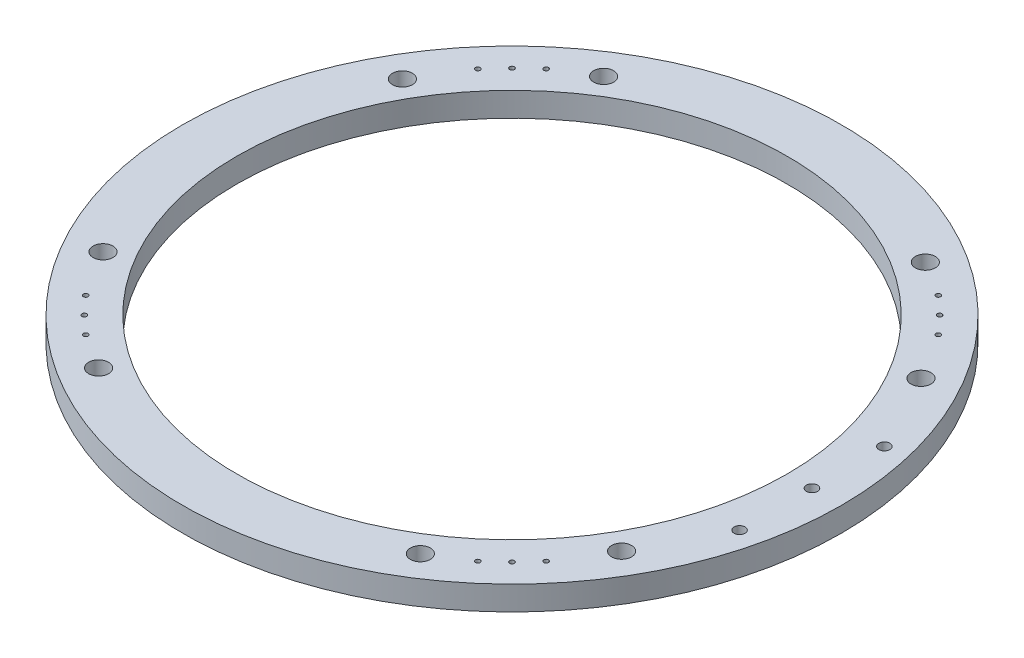
SolidWorks part; units mm, degrees
material "Oak"
ref_plane "Front Plane" through (0, 0, 0) normal (0, 0, 1) x (1, 0, 0)
ref_plane "Top Plane" through (0, 0, 0) normal (0, 1, 0) x (1, 0, 0)
ref_plane "Right Plane" through (0, 0, 0) normal (1, 0, 0) x (0, 0, -1)
sketch "Sketch1" plane through (0, 0, 0) normal (0, 0, 1) x (1, 0, 0)
  line L0 (0, 1125.8152) -> (0, -48874.1848) construction
  line L1 (144.7872, 1009.8532) -> (152.4, 1009.8532)
  line L9 (144.7872, 1022.5532) -> (173.3622, 1022.5532)
  line L10 (144.7872, 1022.5532) -> (144.7872, 1009.8532)
  line L11 (144.7872, 1009.8532) -> (173.3622, 1009.8532)
  line L12 (173.3622, 1022.5532) -> (173.3622, 1009.8532)
revolve "Revolve1" add sketch "Sketch1" angle 360 about L0 region at (159.0747, 1016.2032, 0)
hole_wizard "Tap Drill for M3x0.5 Tap1" positions "Sketch9" profile "Sketch10" hole size "M3x0.5" standard "ANSI Metric" end condition through all
sketch "Sketch9" plane through (0, 1009.8532, 0) normal (0, -1, 0) x (-1, 0, 0)
  line L0 (0, 0) -> (112.4828, 112.4828) construction
  line L3 (0, 0) -> (103.1435, 121.104) construction
  arc A0 (103.1435, 121.104) -> (121.104, 103.1435) centre (0, 0) cw
  circle A1 centre (0, 0) radius 159.0747 construction
  point P0 (103.1435, 121.104)
  point P2 (121.104, 103.1435)
  point P15 (112.4828, 112.4828)
sketch "Sketch10" plane through (-103.1435, 1009.8532, -121.104) normal (1, 0, 0) x (0, 0, -1)
  line L0 (0, 0) -> (0, 12.7)
  line L1 (0, 12.7) -> (1.25, 12.7)
  line L2 (1.25, 12.7) -> (1.25, 0)
  line L5 (1.25, 0) -> (0, 0)
  line L11 (0, -6.35) -> (0, 107.95) construction
  dimension "Thru Hole Dia." = 2.5
  dimension "Thru Hole Depth" = 12.7
pattern_circular "CirPattern1" count 4 over 360 about axis through (0, 1125.8152, 0) along (0, 1, 0) of "Tap Drill for M3x0.5 Tap1"
ref_plane "Plane1" through (0, 1016.2032, 0) normal (0, 1, 0) x (1, 0, 0)
hole_wizard "M5 Clearance Hole1" positions "Sketch14" profile "Sketch15" hole size "M5" standard "ANSI Metric" end condition through all
sketch "Sketch14" plane through (0, 1022.5532, 0) normal (0, 1, 0) x (1, 0, 0)
  line L0 (157.7975, -38.1) -> (157.7975, 38.1) construction
  point P9 (157.7975, -38.1)
  point P12 (157.7975, 0)
  point P14 (157.7975, 38.1)
sketch "Sketch15" plane through (157.7975, 1022.5532, 38.1) normal (1, 0, 0) x (0, 0, 1)
  line L0 (0, 0) -> (0, 12.7)
  line L1 (0, 12.7) -> (2.9, 12.7)
  line L2 (2.9, 12.7) -> (2.9, 0)
  line L5 (2.9, 0) -> (0, 0)
  line L11 (0, -6.35) -> (0, 107.95) construction
  dimension "Thru Hole Dia." = 5.8
  dimension "Thru Hole Depth" = 12.7
hole_wizard "Z (0.413) Diameter Hole1" positions "Sketch16" profile "Sketch17" hole size "Z" standard "ANSI Inch" end condition through all
sketch "Sketch16" plane through (0, 1022.5532, 0) normal (0, 1, 0) x (1, 0, 0)
  line L0 (-136.3879, -78.7436) -> (136.3879, 78.7436) construction
  line L4 (136.3879, -78.7436) -> (-136.3879, 78.7436) construction
  line L6 (0, 0) -> (0, 157.4872) construction
  line L8 (-84.6178, -132.8233) -> (84.6178, 132.8233) construction
  line L11 (-84.6178, 132.8233) -> (84.6178, -132.8233) construction
  circle A0 centre (0, 0) radius 157.4872 construction
  circle A1 centre (0, 0) radius 144.7872 construction
  point P0 (-136.3879, -78.7436)
  point P2 (136.3879, -78.7436)
  point P4 (136.3879, 78.7436)
  point P6 (-136.3879, 78.7436)
  point P37 (-84.6178, 132.8233)
  point P39 (84.6178, 132.8233)
  point P41 (84.6178, -132.8233)
  point P43 (-84.6178, -132.8233)
  dimension "D2" = 12.7
  dimension "D1" = 120
  dimension "D3" = 65
sketch "Sketch17" plane through (-136.3879, 1022.5532, 78.7436) normal (1, 0, 0) x (0, 0, 1)
  line L0 (0, 0) -> (0, 12.7)
  line L1 (0, 12.7) -> (5.2451, 12.7)
  line L2 (5.2451, 12.7) -> (5.2451, 0)
  line L5 (5.2451, 0) -> (0, 0)
  line L11 (0, -6.35) -> (0, 107.95) construction
  dimension "Thru Hole Dia." = 10.4902
  dimension "Thru Hole Depth" = 12.7
sketch "Sketch18" plane through (0, 1022.5532, 0) normal (0, 1, 0) x (1, 0, 0)
  circle A5 centre (-103.1435, 121.104) radius 1.5875
  circle A6 centre (-112.4828, 112.4828) radius 1.5875
  circle A7 centre (-121.104, 103.1435) radius 1.5875
  circle A10 centre (103.1435, 121.104) radius 1.5875
  circle A11 centre (112.4828, 112.4828) radius 1.5875
  circle A12 centre (121.104, 103.1435) radius 1.5875
  circle A14 centre (-121.104, -103.1435) radius 1.5875
  circle A37 centre (-112.4828, -112.4828) radius 1.5875
  circle A38 centre (-103.1435, -121.104) radius 1.5875
  circle A39 centre (103.1435, -121.104) radius 1.5875
  circle A40 centre (112.4828, -112.4828) radius 1.5875
  circle A41 centre (121.104, -103.1435) radius 1.5875
  circle A53 centre (103.1435, 121.104) radius 1.25
  circle A54 centre (103.1435, 121.104) radius 1.25
  circle A55 centre (112.4828, 112.4828) radius 1.25
  circle A56 centre (112.4828, 112.4828) radius 1.25
  circle A57 centre (103.1435, -121.104) radius 1.25
  circle A58 centre (103.1435, -121.104) radius 1.25
  circle A59 centre (-121.104, -103.1435) radius 1.25
  circle A60 centre (-121.104, -103.1435) radius 1.25
  circle A61 centre (-103.1435, -121.104) radius 1.25
  circle A62 centre (-103.1435, -121.104) radius 1.25
  circle A63 centre (-112.4828, -112.4828) radius 1.25
  circle A64 centre (-112.4828, -112.4828) radius 1.25
  circle A65 centre (-103.1435, 121.104) radius 1.25
  circle A66 centre (-103.1435, 121.104) radius 1.25
  circle A67 centre (-121.104, 103.1435) radius 1.25
  circle A68 centre (-121.104, 103.1435) radius 1.25
  circle A69 centre (-112.4828, 112.4828) radius 1.25
  circle A70 centre (-112.4828, 112.4828) radius 1.25
  circle A73 centre (112.4828, -112.4828) radius 1.25
  circle A74 centre (112.4828, -112.4828) radius 1.25
  circle A75 centre (121.104, -103.1435) radius 1.25
  circle A76 centre (121.104, -103.1435) radius 1.25
  circle A77 centre (121.104, 103.1435) radius 1.25
  circle A78 centre (121.104, 103.1435) radius 1.25
  dimension "D13" = 3.175
  dimension "D14" = 0
  dimension "D15" = 0
  dimension "D16" = 0
  dimension "D17" = 0
  dimension "D18" = 0
  dimension "D19" = 0
  dimension "D20" = 0
  dimension "D21" = 0
  dimension "D22" = 0
  dimension "D24" = 0
  dimension "D25" = 0
  dimension "D26" = 0
extrude "Boss-Extrude1" [suppressed] add sketch "Sketch18" against normal up to surface (12.7 mm away) up to face at (-136.3879, 1009.8532, 83.9887)
